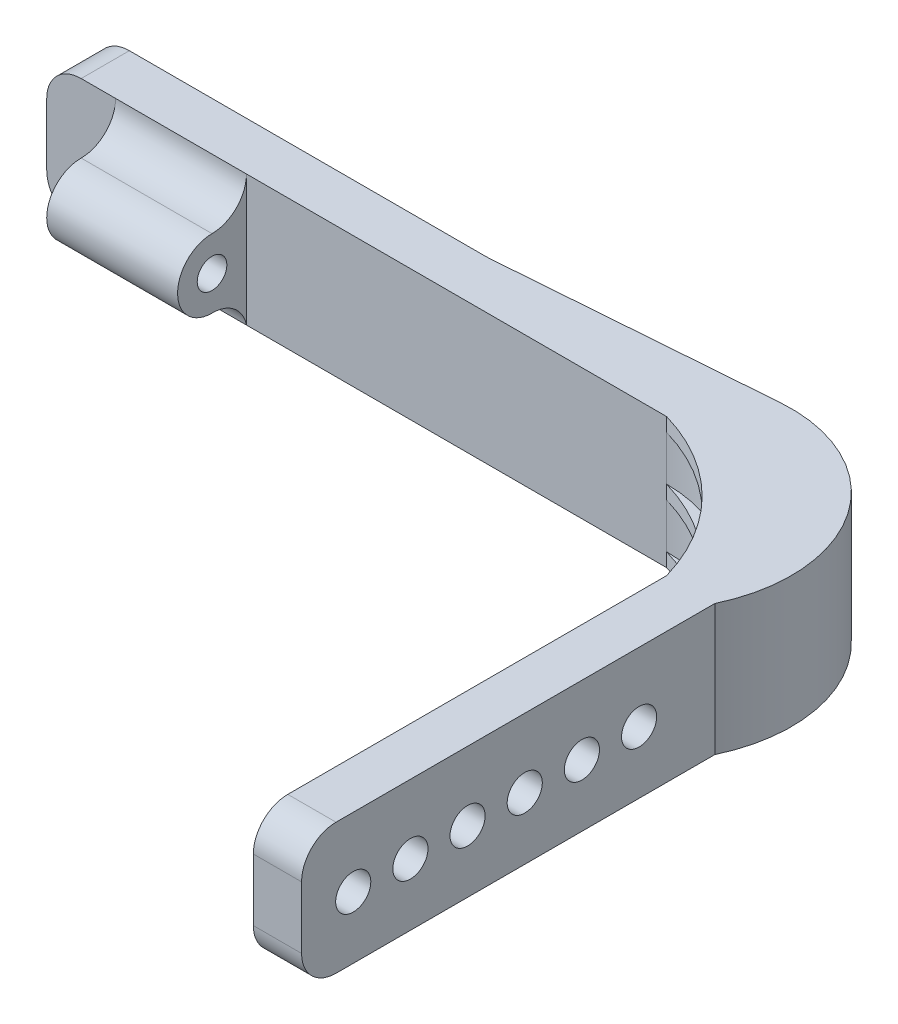
SolidWorks part; units mm, degrees
ref_plane "Front Plane" through (0, 0, 0) normal (0, 0, 1) x (1, 0, 0)
ref_plane "Top Plane" through (0, 0, 0) normal (0, 1, 0) x (1, 0, 0)
ref_plane "Right Plane" through (0, 0, 0) normal (1, 0, 0) x (0, 0, -1)
sketch "Sketch1" plane through (0, 0, 0) normal (0, 1, 0) x (1, 0, 0)
  line L0 (0, 0) -> (90, 0)
  line L1 (117, -27) -> (117, -87)
  line L2 (0, -7) -> (90, -7)
  line L3 (110, -27) -> (110, -87)
  line L4 (110, -87) -> (117, -87)
  line L5 (0, -7) -> (0, 0)
  arc A0 (90, 0) -> (117, -27) centre (90, -27) cw
  arc A1 (90, -7) -> (110, -27) centre (90, -27) cw
  dimension "D4" = 20
  dimension "D2" = 90
  dimension "D3" = 60
  dimension "D1" = 7
extrude "Boss-Extrude1" add sketch "Sketch1" along normal blind 19
ref_plane "Plane1" through (0, 0, 65) normal (0, 0, 1) x (1, 0, 0)
sketch "Sketch3" plane through (0, 0, 65) normal (0, 0, 1) x (1, 0, 0)
  line L6 (117, 11) -> (117, 7)
  line L8 (117, 19) -> (117, 0) construction
  line L9 (117, 7) -> (120, 4)
  line L10 (120, 4) -> (120, 14)
  line L11 (120, 14) -> (117, 11)
  line L12 (117, 9) -> (120, 9) construction
  line L13 (110, 19) -> (117, 19) construction
  dimension "D1" = 10
  dimension "D2" = 4
  dimension "D3" = 3
  dimension "D4" = 10
sketch "Sketch4" plane through (0, 0, 0) normal (1, 0, 0) x (0, 0, -1)
  line L0 (-27, 19) -> (-87, 19) construction
  line L1 (-87, 19) -> (-87, 0) construction
  circle A0 centre (-79.5, 9) radius 2.55
  dimension "D1" = 5.1
  dimension "D2" = 10
  dimension "D3" = 7.5
extrude "Cut-Extrude1" cut sketch "Sketch4" along normal through all
pattern_linear "LPattern1" count 6 spacing 8.3 along (0, 0, -1) of "Cut-Extrude1"
sketch "Sketch5" plane through (0, 0, 0) normal (0, 0, 1) x (1, 0, 0)
  line L0 (90, 19) -> (0, 19) construction
  line L1 (0, 19) -> (0, 0) construction
  circle A0 centre (15, 9) radius 2.55
  dimension "D1" = 5.1
  dimension "D2" = 10
  dimension "D3" = 15
fillet "Fillet2" radius 5 4 edges at (113.5, 0, 87) (113.5, 19, 87) (0, 0, 3.5) (0, 19, 3.5)
sketch "Sketch6" plane through (0, 0, 0) normal (0, 1, 0) x (1, 0, 0)
  line L0 (90, 0) -> (5, 0) construction
  line L1 (57.068, 0) -> (96.4605, 3)
  line L2 (90, 0) -> (57.068, 0)
  line L6 (110, -27) -> (110, -82)
  line L7 (110, -82) -> (117, -82)
  line L8 (117, -82) -> (117, -27)
  line L9 (90, 0) -> (5, 0)
  line L10 (5, 0) -> (5, -7)
  line L11 (5, -7) -> (90, -7)
  arc A0 (117, -27) -> (96.4605, 3) centre (98.0552, -17.9394) ccw
  arc A3 (117, -27) -> (90, 0) centre (90, -27) ccw
  arc A8 (117, -27) -> (90, 0) centre (90, -27) ccw
  arc A9 (110, -27) -> (90, -7) centre (90, -27) ccw
  dimension "D2" = 21
  dimension "D3" = 3
  dimension "D1" = 0
extrude "Boss-Extrude4" add sketch "Sketch6" along normal up to surface (19 mm away) up to face at (81.7168, 19, 27.7832)
sketch "Sketch8" plane through (0, 0, 0) normal (0, 1, 0) x (1, 0, 0)
  arc A0 (90, -7) -> (110, -27) centre (81.8988, -35.1012) cw
  arc A1 (90, -7) -> (110, -27) centre (90, -27) cw
extrude "Boss-Extrude5" add sketch "Sketch8" along normal blind 2
pattern_linear "LPattern3" count 3 spacing 8.5 along (0, 1, 0) of "Boss-Extrude5"
fillet "Fillet4" radius 20 1 edges at (57.068, 9.5, 0)
ref_plane "Plane2" through (10, 0, 0) normal (-1, 0, 0) x (0, 0, 1)
sketch "Sketch9" plane through (10, 0, 0) normal (-1, 0, 0) x (0, 0, 1)
  line L0 (2.3062, 9) -> (15.0365, 9) construction
  line L1 (0, 19) -> (7, 19) construction
  line L2 (7, 14) -> (12, 14)
  line L3 (7, 17) -> (7, 10.5) construction
  line L4 (7, 4) -> (12, 4)
  line L5 (7, 8.5) -> (7, 2) construction
  line L6 (7, 14) -> (7, 4)
  arc A0 (12, 14) -> (12, 4) centre (12, 9) cw
  circle A1 centre (12, 9) radius 2.15
  point P16 (17, 9)
  dimension "D6" = 5
  dimension "D7" = 4.3
  dimension "D1" = 10
  dimension "D2" = 5
  dimension "D3" = 5
  dimension "D4" = 5
  dimension "D5" = 5
  dimension "D8" = 5
extrude "Boss-Extrude6" add sketch "Sketch9" against normal blind 19
fillet "Fillet5" radius 5 2 edges at (19.5, 4, 7) (19.5, 14, 7)
